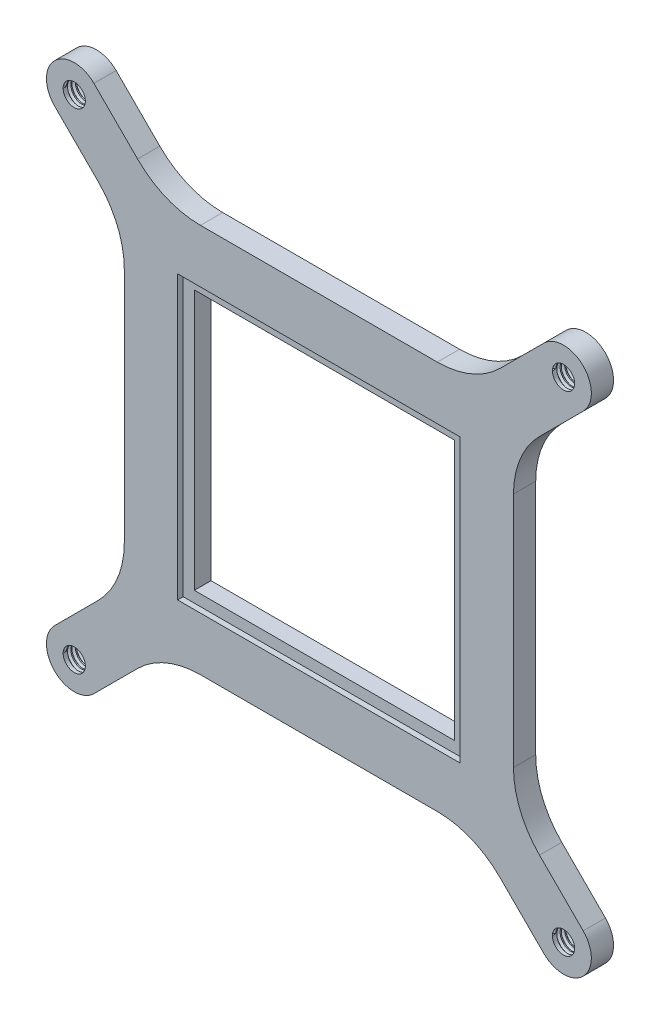
SolidWorks part; units mm, degrees
ref_plane "Front Plane" through (0, 0, 0) normal (0, 0, 1) x (1, 0, 0)
ref_plane "Top Plane" through (0, 0, 0) normal (0, 1, 0) x (1, 0, 0)
ref_plane "Right Plane" through (0, 0, 0) normal (1, 0, 0) x (0, 0, -1)
sketch "Sketch1" plane through (0, 0, 0) normal (0, 0, 1) x (1, 0, 0)
  line L0 (-23.6997, 22.7421) -> (-19.1997, 18.2421) construction
  line L1 (-12.3505, 18.2421) -> (8.9482, 18.2421)
  line L2 (-19.1997, 11.3901) -> (-19.1997, -9.9058)
  line L3 (-12.3505, -16.7579) -> (8.9482, -16.7579)
  line L4 (15.8003, 11.3901) -> (15.8003, -9.9058)
  line L5 (-13.3997, 12.4421) -> (10.0003, 12.4421)
  line L6 (-13.3997, 12.4421) -> (-13.3997, -10.9579)
  line L7 (-13.3997, -10.9579) -> (10.0003, -10.9579)
  line L8 (10.0003, 12.4421) -> (10.0003, -10.9579)
  line L9 (-23.6997, 22.7421) -> (-25.4675, 20.9744) construction
  line L10 (-25.4675, 20.9744) -> (-21.932, 24.5099) construction
  line L11 (-21.932, 24.5099) -> (-18.0073, 20.5853)
  line L12 (-25.4675, 20.9744) -> (-21.5409, 17.0449)
  line L13 (-15.6642, 18.2421) -> (-15.6642, -16.7579) construction
  line L14 (-19.1997, 14.7021) -> (15.8003, 14.7021) construction
  line L15 (12.2603, 18.2421) -> (12.2603, -16.7579) construction
  line L16 (15.8003, -13.2179) -> (-19.1997, -13.2179) construction
  line L17 (18.1414, 17.0449) -> (22.0687, 20.975)
  line L18 (18.1414, -15.5607) -> (22.0687, -19.4907)
  line L19 (14.6031, 20.5833) -> (18.5331, 24.5105)
  line L20 (14.6031, -19.099) -> (18.5331, -23.0263)
  line L21 (-21.5409, -15.5607) -> (-25.4681, -19.4907)
  line L22 (-18.0073, -19.101) -> (-21.932, -23.0256)
  circle A0 centre (-23.6997, 22.7421) radius 1
  arc A1 (-21.932, 24.5099) -> (-25.4675, 20.9744) centre (-23.6997, 22.7421) ccw
  arc A2 (22.0687, 20.975) -> (18.5331, 24.5105) centre (20.3003, 22.7421) ccw
  circle A3 centre (20.3003, 22.7421) radius 1
  arc A4 (18.5331, -23.0263) -> (22.0687, -19.4907) centre (20.3003, -21.2579) ccw
  circle A5 centre (20.3003, -21.2579) radius 1
  arc A6 (-25.4681, -19.4907) -> (-21.932, -23.0256) centre (-23.6997, -21.2579) ccw
  circle A7 centre (-23.6997, -21.2579) radius 1
  arc A8 (-21.5409, 17.0449) -> (-19.1997, 11.3901) centre (-27.1997, 11.3901) cw
  arc A9 (-18.0073, 20.5853) -> (-12.3505, 18.2421) centre (-12.3505, 26.2421) ccw
  arc A10 (8.9482, 18.2421) -> (14.6031, 20.5833) centre (8.9482, 26.2421) ccw
  arc A11 (15.8003, 11.3901) -> (18.1414, 17.0449) centre (23.8003, 11.3901) cw
  arc A12 (18.1414, -15.5607) -> (15.8003, -9.9058) centre (23.8003, -9.9058) cw
  arc A13 (8.9482, -16.7579) -> (14.6031, -19.099) centre (8.9482, -24.7579) cw
  arc A14 (-19.1997, -9.9058) -> (-21.5409, -15.5607) centre (-27.1997, -9.9058) cw
  arc A15 (-12.3505, -16.7579) -> (-18.0073, -19.101) centre (-12.3505, -24.7579) ccw
  dimension "D7" = 10.3
  dimension "D8" = 2
  dimension "D2" = 8
  dimension "D3" = 23.4
  dimension "D4" = 23.4
  dimension "D5" = 5.8
  dimension "D6" = 5.8
  dimension "D10" = 10.3
  dimension "D11" = 3.5355
  dimension "D12" = 3.54
  dimension "D13" = 3.54
  dimension "D9" = 2
extrude "Boss-Extrude1" add sketch "Sketch1" along normal blind 2
sketch "Sketch2" plane through (0, 0, 2) normal (0, 0, 1) x (1, 0, 0)
  line L0 (10.0003, -10.9579) -> (10.0003, 12.4421) construction
  line L1 (-14.3997, 13.4421) -> (11.0003, 13.4421)
  line L2 (-14.3997, 13.4421) -> (-14.3997, -11.9579)
  line L3 (-14.3997, -11.9579) -> (11.0003, -11.9579)
  line L4 (11.0003, 13.4421) -> (11.0003, -11.9579)
  line L5 (10.0003, 12.4421) -> (-13.3997, 12.4421) construction
  dimension "D1" = 25.4
  dimension "D2" = 25.4
  dimension "D3" = 1
  dimension "D4" = 1
extrude "Cut-Extrude1" cut sketch "Sketch2" against normal blind 0.5
thread "Thread1" pitch 0.4 method cut profile "Thread Profile1" start angle 0, offset 0, length 2, pitch 0.4, diameter 2
ref_plane "Plane1" through (-24.6997, 22.7421, 2) normal (0, -1, 0) x (-1, 0, 0)
sketch "Thread Profile1" plane through (-24.6997, 22.7421, 2) normal (0, -1, 0) x (-1, 0, 0)
  line L0 (0, 0) -> (0, 0.4) construction
  line L1 (0, 0) -> (0.2165, 0.125)
  line L2 (0.2165, 0.125) -> (0.2165, 0.175)
  line L3 (0.2165, 0.175) -> (0, 0.3)
  line L4 (0.2165, 0.15) -> (0, 0.15) construction
  line L11 (0, 0) -> (0, 0.3)
  point P2 (0, 0)
  dimension "Pitch" = 0.4
  dimension "Profile_Angle" = 60
  dimension "Profile_Land" = 0.05
  dimension "Profile_Height" = 0.2165
thread "Thread2" pitch 0.4 method cut profile "Thread Profile2" start angle 0, offset 0, length 2, pitch 0.4, diameter 2
ref_plane "Plane2" through (19.3003, 22.7421, 2) normal (0, -1, 0) x (-1, 0, 0)
sketch "Thread Profile2" plane through (19.3003, 22.7421, 2) normal (0, -1, 0) x (-1, 0, 0)
  line L0 (0, 0) -> (0, 0.4) construction
  line L1 (0, 0) -> (0.2165, 0.125)
  line L2 (0.2165, 0.125) -> (0.2165, 0.175)
  line L3 (0.2165, 0.175) -> (0, 0.3)
  line L4 (0.2165, 0.15) -> (0, 0.15) construction
  line L11 (0, 0) -> (0, 0.3)
  point P2 (0, 0)
  dimension "Pitch" = 0.4
  dimension "Profile_Angle" = 60
  dimension "Profile_Land" = 0.05
  dimension "Profile_Height" = 0.2165
thread "Thread3" pitch 0.4 method cut profile "Thread Profile3" start angle 0, offset 0, length 2, pitch 0.4, diameter 2
ref_plane "Plane3" through (-24.6997, -21.2579, 2) normal (0, -1, 0) x (-1, 0, 0)
sketch "Thread Profile3" plane through (-24.6997, -21.2579, 2) normal (0, -1, 0) x (-1, 0, 0)
  line L0 (0, 0) -> (0, 0.4) construction
  line L1 (0, 0) -> (0.2165, 0.125)
  line L2 (0.2165, 0.125) -> (0.2165, 0.175)
  line L3 (0.2165, 0.175) -> (0, 0.3)
  line L4 (0.2165, 0.15) -> (0, 0.15) construction
  line L11 (0, 0) -> (0, 0.3)
  point P2 (0, 0)
  dimension "Pitch" = 0.4
  dimension "Profile_Angle" = 60
  dimension "Profile_Land" = 0.05
  dimension "Profile_Height" = 0.2165
thread "Thread4" pitch 0.4 method cut profile "Thread Profile4" start angle 0, offset 0, length 2, pitch 0.4, diameter 2
ref_plane "Plane4" through (19.3003, -21.2579, 2) normal (0, -1, 0) x (-1, 0, 0)
sketch "Thread Profile4" plane through (19.3003, -21.2579, 2) normal (0, -1, 0) x (-1, 0, 0)
  line L0 (0, 0) -> (0, 0.4) construction
  line L1 (0, 0) -> (0.2165, 0.125)
  line L2 (0.2165, 0.125) -> (0.2165, 0.175)
  line L3 (0.2165, 0.175) -> (0, 0.3)
  line L4 (0.2165, 0.15) -> (0, 0.15) construction
  line L11 (0, 0) -> (0, 0.3)
  point P2 (0, 0)
  dimension "Pitch" = 0.4
  dimension "Profile_Angle" = 60
  dimension "Profile_Land" = 0.05
  dimension "Profile_Height" = 0.2165
